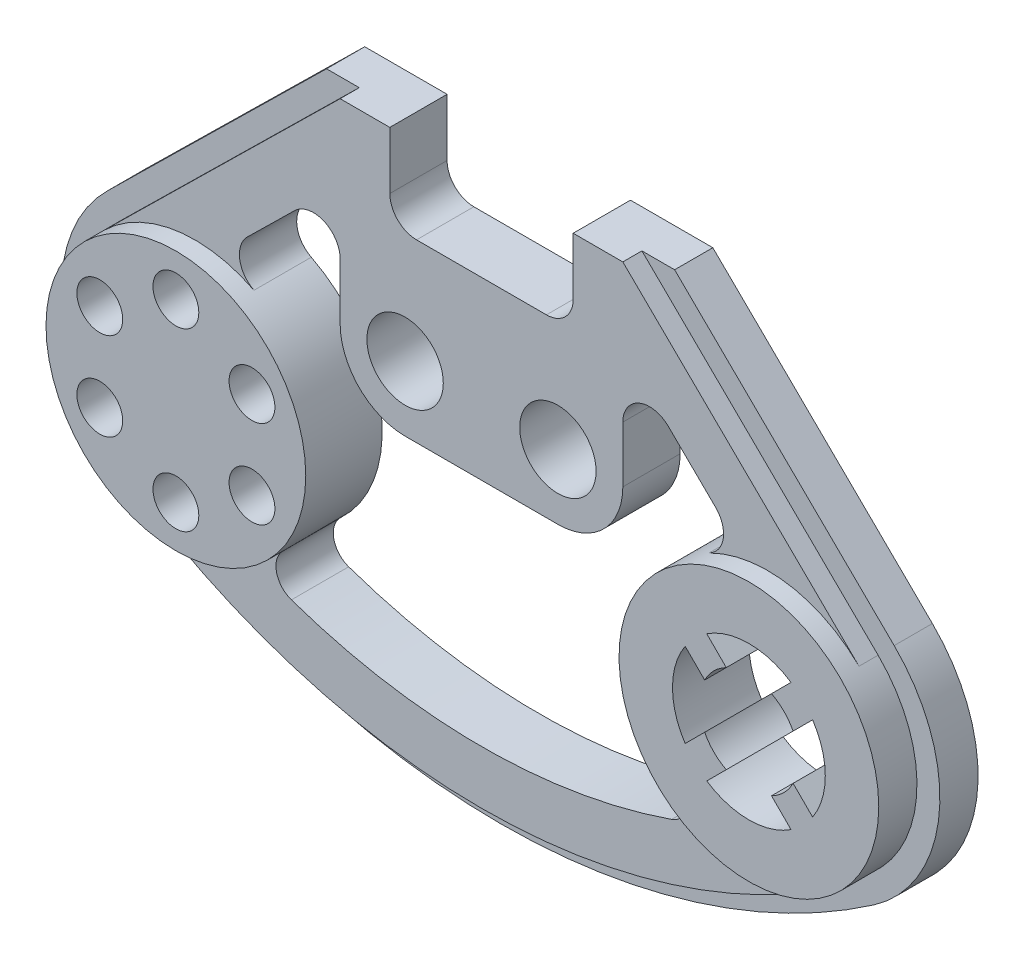
SolidWorks part; units mm, degrees
ref_plane "Спереди" through (0, 0, 0) normal (0, 0, 1) x (1, 0, 0)
ref_plane "Сверху" through (0, 0, 0) normal (0, 1, 0) x (1, 0, 0)
ref_plane "Справа" through (0, 0, 0) normal (1, 0, 0) x (0, 0, -1)
sketch "Эскиз1" plane through (0, 0, 0) normal (0, 0, 1) x (1, 0, 0)
  line L0 (0, 0) -> (0, 46) construction
  line L1 (0, 0) -> (-42.3111, 0) construction
  line L2 (150, 0) -> (150, 41.7935) construction
  line L3 (150, 0) -> (118.9946, 31.0054) construction
  line L4 (133.3152, 11.028) -> (138.4251, 5.918)
  line L5 (138.972, 16.6848) -> (144.082, 11.5749)
  line L6 (150, 0) -> (186.8718, 36.8718) construction
  line L7 (138.4251, -5.918) -> (133.3152, -11.028)
  line L8 (0, 0) -> (75, 0) construction
  line L9 (166.6848, 11.028) -> (161.5749, 5.918)
  line L10 (161.028, 16.6848) -> (155.918, 11.5749)
  line L11 (161.5749, -5.918) -> (166.6848, -11.028)
  line L12 (155.918, -11.5749) -> (161.028, -16.6848)
  line L13 (144.082, -11.5749) -> (138.972, -16.6848)
  line L14 (75, 0) -> (75, 85) construction
  line L15 (75, 85) -> (112, 85) construction
  line L16 (112, 85) -> (173.8286, 24.2528)
  line L17 (75, 85) -> (38, 85) construction
  line L18 (38, 85) -> (-23.8286, 24.2528)
  line L19 (120.5611, 85) -> (178.0337, 28.5327)
  line L20 (29.4389, 85) -> (-28.0337, 28.5327)
  line L21 (13.7201, 41.5182) -> (26.0941, 53.6757)
  line L22 (29.4389, 85) -> (38, 85)
  line L23 (38, 48.6825) -> (38, 34)
  line L24 (55, 17) -> (95, 17)
  line L25 (112, 48.6825) -> (112, 34)
  line L26 (136.2799, 41.5182) -> (123.9059, 53.6757)
  line L27 (120.5611, 85) -> (112, 85)
  line L28 (38, 85) -> (51, 85)
  line L29 (112, 85) -> (99, 85)
  line L30 (51, 85) -> (51, 70)
  line L31 (99, 85) -> (99, 70)
  line L32 (58, 63) -> (92, 63)
  circle A0 centre (0, 0) radius 34
  circle A1 centre (0, 23) radius 6
  circle A2 centre (19.9186, 11.5) radius 6
  circle A3 centre (19.9186, -11.5) radius 6
  circle A4 centre (0, -23) radius 6
  circle A5 centre (-19.9186, -11.5) radius 6
  circle A6 centre (-19.9186, 11.5) radius 6
  circle A7 centre (150, 0) radius 34
  arc A8 (133.3152, 11.028) -> (133.3152, -11.028) centre (150, 0) ccw
  arc A9 (155.918, -11.5749) -> (161.5749, -5.918) centre (150, 0) ccw
  arc A10 (138.4251, -5.918) -> (144.082, -11.5749) centre (150, 0) ccw
  arc A11 (144.082, 11.5749) -> (138.4251, 5.918) centre (150, 0) ccw
  arc A12 (161.5749, 5.918) -> (155.918, 11.5749) centre (150, 0) ccw
  arc A13 (138.972, -16.6848) -> (161.028, -16.6848) centre (150, 0) ccw
  arc A14 (166.6848, -11.028) -> (166.6848, 11.028) centre (150, 0) ccw
  arc A15 (161.028, 16.6848) -> (138.972, 16.6848) centre (150, 0) ccw
  arc A16 (-19.3182, -27.9787) -> (169.3182, -27.9787) centre (75, 108.6232) ccw
  arc A17 (-22.7273, -32.9161) -> (172.7273, -32.9161) centre (75, 108.6232) ccw
  arc A18 (25.2342, -34.9991) -> (124.7658, -34.9991) centre (75, 108.6232) ccw
  arc A19 (-28.0337, 28.5327) -> (-22.7273, -32.9161) centre (0, 0) ccw
  arc A20 (172.7273, -32.9161) -> (178.0337, 28.5327) centre (150, 0) ccw
  arc A21 (23.1188, -24.9303) -> (25.2342, -34.9991) centre (27.1986, -29.3298) ccw
  arc A22 (124.7658, -34.9991) -> (126.8812, -24.9303) centre (122.8014, -29.3298) ccw
  arc A23 (13.7201, 41.5182) -> (15.446, 30.289) centre (18.626, 36.5249) ccw
  arc A24 (38, 48.6825) -> (26.0941, 53.6757) centre (31, 48.6825) ccw
  arc A25 (38, 34) -> (55, 17) centre (55, 34) ccw
  circle A26 centre (95, 34) radius 10
  circle A27 centre (55, 34) radius 10
  arc A28 (112, 34) -> (95, 17) centre (95, 34) cw
  arc A29 (112, 48.6825) -> (123.9059, 53.6757) centre (119, 48.6825) cw
  arc A30 (136.2799, 41.5182) -> (134.554, 30.289) centre (131.374, 36.5249) cw
  arc A31 (51, 70) -> (58, 63) centre (58, 70) ccw
  arc A32 (92, 63) -> (99, 70) centre (92, 70) ccw
  point P20 (0, 0)
  dimension "D1" = 68
  dimension "D2" = 12
  dimension "D5" = 68
  dimension "D7" = 40
  dimension "D9" = 26
  dimension "D15" = 166
  dimension "D16" = 6
  dimension "D22" = 40
  dimension "D23" = 40
  dimension "D24" = 152
  dimension "D25" = 6
  dimension "D26" = 6
  dimension "D28" = 7
  dimension "D29" = 7
  dimension "D32" = 17
  dimension "D34" = 20
  dimension "D37" = 7
  dimension "D38" = 7
  dimension "D3" = 23
  dimension "D6" = 150
  dimension "D8" = 45
  dimension "D10" = 4
  dimension "D11" = 8
  dimension "D12" = 45
  dimension "D13" = 4
  dimension "D14" = 4
  dimension "D17" = 75
  dimension "D18" = 85
  dimension "D19" = 90
  dimension "D20" = 74
  dimension "D21" = 37
  dimension "D27" = 14
  dimension "D30" = 13
  dimension "D31" = 34
  dimension "D33" = 20
  dimension "D35" = 61
  dimension "D36" = 22
  dimension "D4" = 6
extrude "Бобышка-Вытянуть1" add sketch "Эскиз1" along normal blind 10 contours A17 A20 L19 L27 L16 A7 A16 A0 L18 L22 L20 A19 region at (116.2806, 82.2629, 0)
extrude "Бобышка-Вытянуть2" add sketch "Эскиз1<3>" along normal blind 20 contours A0 A6 A5 A4 A3 A2 A1 | A7 A15 L10 A12 L9 A14 L11 A9 L12 A13 L13 A10 L7 A8 L4 A11 L5 region at (180.4674, 12.7777, 0) region at (0, 0, 0)
sketch "Эскиз1<3>" plane through (0, 0, 0) normal (0, 0, 1) x (1, 0, 0) same geometry as "Эскиз1"
extrude "Бобышка-Вытянуть3" add sketch "Эскиз1<4>" along normal blind 15 contours A32 L32 A31 L30 L28 L18 A0 A23 L21 A24 L23 A25 L24 A28 L25 A29 L26 A30 A7 L16 L29 L31 A26 A27 | A22 A18 A21 A0 A16 A7 region at (75, 50.219, 0) region at (75, -44.4617, 0)
sketch "Эскиз1<4>" plane through (0, 0, 0) normal (0, 0, 1) x (1, 0, 0) same geometry as "Эскиз1"
